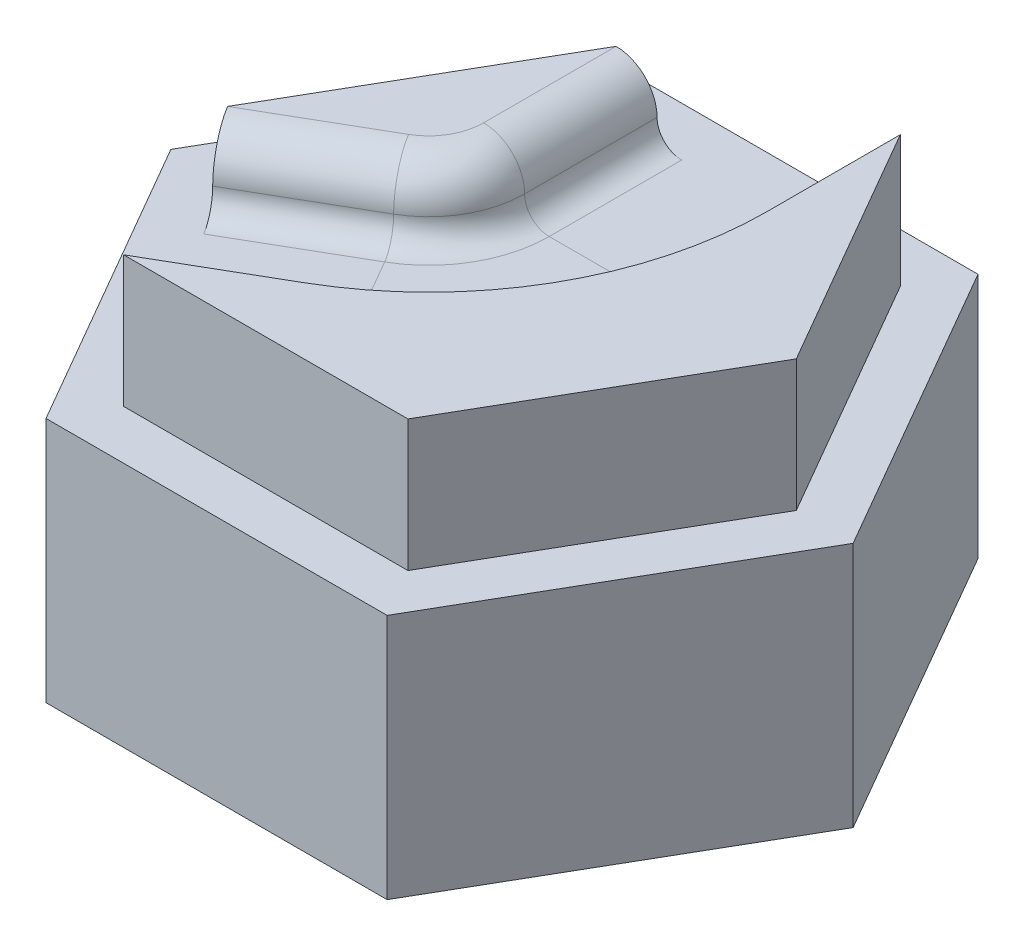
SolidWorks part; units mm, degrees
ref_plane "Front Plane" through (0, 0, 0) normal (0, 0, 1) x (1, 0, 0)
ref_plane "Top Plane" through (0, 0, 0) normal (0, 1, 0) x (1, 0, 0)
ref_plane "Right Plane" through (0, 0, 0) normal (1, 0, 0) x (0, 0, -1)
sketch "Sketch1" plane through (0, 0, 0) normal (0, 1, 0) x (1, 0, 0)
  line L1 (10.3923, 0) -> (5.1962, 9)
  line L2 (5.1962, 9) -> (-5.1962, 9)
  line L3 (-5.1962, 9) -> (-10.3923, 0)
  line L4 (-10.3923, 0) -> (-5.1962, -9)
  line L5 (-5.1962, -9) -> (5.1962, -9)
  line L6 (5.1962, -9) -> (10.3923, 0)
  line L7 (8.6603, 0) -> (4.3301, 7.5)
  line L8 (4.3301, 7.5) -> (-4.3301, 7.5)
  line L9 (-4.3301, 7.5) -> (-8.6603, 0)
  line L10 (-8.6603, 0) -> (-4.3301, -7.5)
  line L11 (-4.3301, -7.5) -> (4.3301, -7.5)
  line L12 (4.3301, -7.5) -> (8.6603, 0)
  circle A0 centre (0, 0) radius 9 construction
  circle A1 centre (0, 0) radius 7.5 construction
  dimension "D1" = 18
  dimension "D2" = 1.5
extrude "Boss-Extrude1" add sketch "Sketch1" along normal blind 7.5 contours L11 L12 L7 L8 L9 L10 | L5 L6 L1 L2 L3 L4 L12 L11 L10 L9 L8 L7 region at (7.5561, 0, 4.3625) region at (0, 0, 0)
extrude "Cut-Extrude1" cut sketch "Sketch1<3>" along normal blind 2 contours L11 L12 L7 L8 L9 L10 region at (0, 0, 0)
sketch "Sketch1<3>" plane through (0, 0, 0) normal (0, 1, 0) x (1, 0, 0) same geometry as "Sketch1"
sketch "Sketch4" plane through (0, 7.5, 0) normal (0, 1, 0) x (1, 0, 0)
  line L0 (10.3923, 0) -> (5.1962, 9) construction
  line L1 (8.6603, 0) -> (4.3301, 7.5)
  line L2 (4.3301, 7.5) -> (-4.3301, 7.5)
  line L3 (-4.3301, 7.5) -> (-8.6603, 0)
  line L4 (-8.6603, 0) -> (-4.3301, -7.5)
  line L5 (-4.3301, -7.5) -> (4.3301, -7.5)
  line L6 (4.3301, -7.5) -> (8.6603, 0)
  circle A0 centre (0, 0) radius 7.5 construction
  dimension "D1" = 1.5
extrude "Boss-Extrude2" add sketch "Sketch4" along normal blind 2
sketch "Sketch5" plane through (-6.4952, 0, 3.75) normal (-0.866, 0, 0.5) x (0.5, 0, 0.866)
  line L1 (-4.3301, 7.5) -> (4.3301, 7.5) construction
  line L4 (0, 7.5) -> (0, 9.5) construction
  line L5 (-4.3301, 9.5) -> (4.3301, 9.5) construction
  line L9 (-4.3301, 9.5) -> (4.3301, 9.5)
  line L11 (-2.3301, 7.5) -> (2.3301, 7.5)
  arc A1 (-3.0801, 8.25) -> (-4.3301, 9.5) centre (-4.3301, 8.25) ccw
  arc A2 (-3.0801, 8.25) -> (-2.3301, 7.5) centre (-2.3301, 8.25) ccw
  arc A3 (3.0801, 8.25) -> (4.3301, 9.5) centre (4.3301, 8.25) cw
  arc A4 (3.0801, 8.25) -> (2.3301, 7.5) centre (2.3301, 8.25) cw
  dimension "D2" = 2.5
sketch "Sketch7" plane through (0, 9.5, 0) normal (0, 1, 0) x (1, 0, 0)
  line L0 (-6.4952, -3.75) -> (-3, -1.7321)
  line L1 (-7.6603, -1.7321) -> (-5.3301, -5.7679) construction
  line L2 (0, 3.4641) -> (0, 7.5)
  line L3 (4.3301, 7.5) -> (-4.3301, 7.5) construction
  arc A0 (-3, -1.7321) -> (0, 3.4641) centre (-6, 3.4641) ccw
  point P10 (0, 0)
  dimension "D1" = 6
sweep "Cut-Sweep3" cut profiles "Sketch5" path "Sketch7"
sketch "Sketch8" plane through (0, 9.5, 0) normal (0, 1, 0) x (1, 0, 0)
  line L5 (-0.8349, -5.4821) -> (-4.3301, -7.5)
  line L6 (-4.3301, -7.5) -> (4.3301, -7.5)
  line L7 (4.3301, -7.5) -> (8.6603, 0)
  line L8 (8.6603, 0) -> (4.3301, 7.5)
  line L9 (4.3301, 7.5) -> (4.3301, 3.4641)
  line L10 (-0.8349, -5.4821) -> (-4.3301, -7.5)
  line L11 (-4.3301, -7.5) -> (4.3301, -7.5)
  line L12 (4.3301, -7.5) -> (8.6603, 0)
  line L13 (8.6603, 0) -> (4.3301, 7.5)
  line L14 (4.3301, 7.5) -> (4.3301, 3.4641)
  arc A1 (-0.8349, -5.4821) -> (4.3301, 3.4641) centre (-6, 3.4641) ccw
  arc A2 (-0.8349, -5.4821) -> (4.3301, 3.4641) centre (-6, 3.4641) ccw
  dimension "D1" = 0
extrude "Boss-Extrude3" add sketch "Sketch8" along normal blind 2
